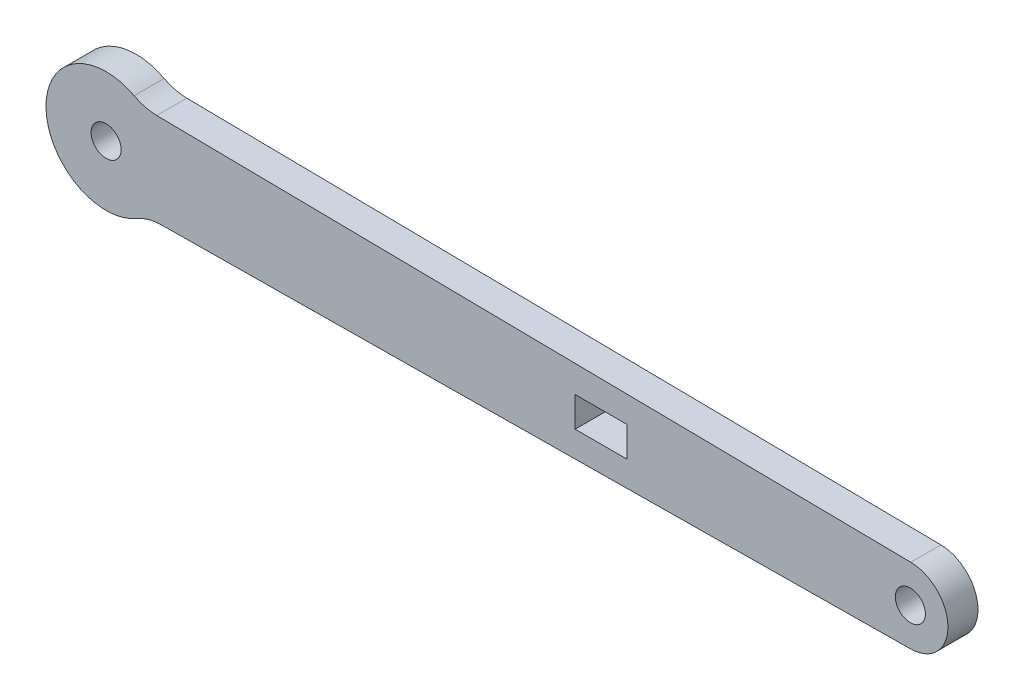
SolidWorks part; units mm, degrees
ref_plane "Plan de face" through (0, 0, 0) normal (0, 0, 1) x (1, 0, 0)
ref_plane "Plan de dessus" through (0, 0, 0) normal (0, 1, 0) x (1, 0, 0)
ref_plane "Plan de droite" through (0, 0, 0) normal (1, 0, 0) x (0, 0, -1)
sketch "Esquisse1" plane through (0, 0, 0) normal (0, 0, 1) x (1, 0, 0)
  line L0 (3.8678, 10.6672) -> (93.8645, 11.4353) construction
  line L1 (3.8122, 4.9787) -> (93.8122, 4.9787) construction
  line L2 (3.8122, 4.9787) -> (3.8122, 16.9787) construction
  line L3 (3.8122, 16.9787) -> (93.8122, 16.9787) construction
  line L4 (93.8122, 4.9787) -> (93.8122, 16.9787) construction
  line L5 (3.8122, 10.9787) -> (93.8122, 10.9787) construction
  line L6 (14.8705, 15.7129) -> (90.1112, 14.7284)
  line L7 (90.0622, 7.2287) -> (15.3348, 6.494)
  line L9 (56.6122, 12.4787) -> (61.8122, 12.4787)
  line L10 (56.6122, 12.4787) -> (56.6122, 9.4787)
  line L11 (56.6122, 9.4787) -> (61.8122, 9.4787)
  line L12 (61.8122, 12.4787) -> (61.8122, 9.4787)
  circle A0 centre (9.8122, 10.9787) radius 1.5
  arc A1 (12.6069, 16.2881) -> (12.8513, 5.8054) centre (9.8122, 10.9787) ccw
  arc A3 (90.0622, 7.2287) -> (90.1112, 14.7284) centre (90.0622, 10.9787) ccw
  arc A4 (15.3348, 6.494) -> (12.8513, 5.8054) centre (15.3839, 1.4942) ccw
  arc A5 (14.8705, 15.7129) -> (12.6069, 16.2881) centre (14.9359, 20.7125) cw
  circle A6 centre (90.0622, 10.9787) radius 1.5
  point P18 (13.7808, 6.4787)
  dimension "D4" = 3
  dimension "D6" = 7.5
  dimension "D7" = 4.8
  dimension "D9" = 5
  dimension "D14" = 3
  dimension "D1" = 90
  dimension "D2" = 12
  dimension "D3" = 90
  dimension "D5" = 4.5
  dimension "D8" = 4.5
  dimension "D10" = 5.2
  dimension "D11" = 3
  dimension "D12" = 1.5
  dimension "D13" = 32
base flange "Tôle de base pliée1" sketch "Esquisse1" thickness 3 reverse thickness direction no parameters "D1"=1.5
sketch "Lignes de pliage1" [suppressed] plane through (0, 0, 0) normal (0, 1, 0) x (1, 0, 0)
sketch "Cube de visualisation1" [suppressed] plane through (0, 0, 0) normal (0, 1, 0) x (1, 0, 0)
sheet metal parameters "Tôlerie1" thickness 3 parameters "D1"=1.5
flat pattern "Etat déplié1" [suppressed]
sketch "Lignes de pliage2" plane through (0, 0, 0) normal (0, 1, 0) x (1, 0, 0)
sketch3d "Cube de visualisation2" [suppressed]
  line L0 (-11.4011, 15.6502, 0) -> (78.5319, 13.1278, 0) construction
  line L1 (-11.7375, 3.6551, 0) -> (78.1954, 1.1326, 0) construction
  line L2 (-11.4011, 15.6502, 0) -> (-11.7375, 3.6551, 0) construction
  line L3 (78.5319, 13.1278, 0) -> (78.1954, 1.1326, 0) construction
